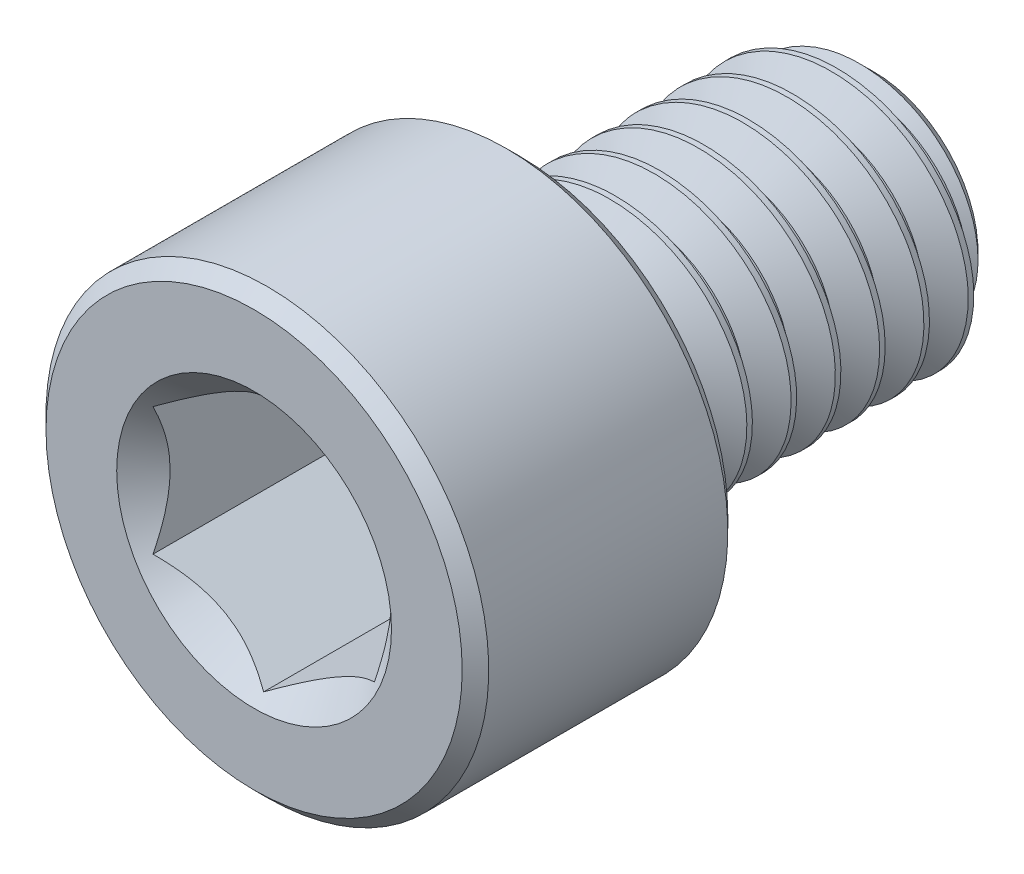
SolidWorks part; units mm, degrees
ref_plane "Front Plane" through (0, 0, 0) normal (0, 0, 1) x (1, 0, 0)
ref_plane "Top Plane" through (0, 0, 0) normal (0, 1, 0) x (1, 0, 0)
ref_plane "Right Plane" through (0, 0, 0) normal (1, 0, 0) x (0, 0, -1)
sketch "Sketch1" plane through (0, 0, 0) normal (1, 0, 0) x (0, 0, -1)
  line L0 (-7, 0) -> (7, 0) construction
  line L1 (7, 0) -> (7, 2.3505) construction
  line L2 (7, 2.3505) -> (6.3505, 3) construction
  line L3 (6.3505, 3) -> (6.25, 3) construction
  line L4 (6.25, 3) -> (-1, 3) construction
  line L5 (-1, 3) -> (-1, 5) construction
  line L6 (-1, 5) -> (-7, 5) construction
  line L7 (-7, 5) -> (-7, 0) construction
  line L8 (7, 2.3505) -> (7, 3) construction
  line L9 (6.9375, 3.1083) -> (7.4375, 2.2422) construction
  line L10 (7.4375, 2.2422) -> (7.9375, 3.1083) construction
  line L11 (7.9375, 3.1083) -> (6.9375, 3.1083) construction
  line L12 (7.4375, 3.1083) -> (7.4375, 3) construction
  line L13 (7.4375, 2.2422) -> (7.4375, 2.3505) construction
  line L14 (7.375, 2.3505) -> (7.5, 2.3505) construction
  line L15 (7, 3) -> (7.875, 3) construction
  line L16 (6.9687, 3.0541) -> (7.9063, 3.0541) construction
  line L17 (7, 0) -> (7, -3) construction
  line L18 (-1.3, 5) -> (-1, 4.7) construction
  line L19 (-6.7, 5) -> (-7, 4.7) construction
  line L20 (-1, 3) -> (-1, 0) construction
  line L21 (-1, 1.5) -> (1.6667, 1.5) construction
  line L22 (1.6667, 1.5) -> (4.3333, 1.5) construction
  line L23 (4.3333, 1.5) -> (7, 1.5) construction
  line L24 (1.6667, 1.5) -> (1.6667, 3) construction
  line L25 (1.6667, 3) -> (1.6667, 5) construction
  line L26 (4.3333, 1.5) -> (4.3333, 5) construction
  point P0 (-7, 2.5)
  point P3 (4.5, 3)
  point P4 (0, 0)
  point P18 (4.3333, 3)
  point P22 (7.4375, 2.3505)
  point P24 (6.25, 3)
  point P25 (7.4375, 3)
  point P28 (7.4375, 3.0541)
  point P29 (4.5, -3)
  point P30 (1.6667, 3)
  point P31 (-4, 5)
  point P37 (-2.05, 5)
  point P38 (-6.55, 5)
  point P45 (1.6667, 1.5)
  point P46 (4.3333, 1.5)
  dimension "D2" = 0.125
  dimension "D7" = 0.3
  dimension "D8" = 0.3
  dimension "D9" = 0.3
  dimension "D10" = 0.15
  dimension "D11" = 0.75
  dimension "Drive Size" = 5
  dimension "Head Diameter" = 10
  dimension "Head Height" = 6
  dimension "Thread Pitch" = 1
  dimension "Thread Dia" = 6
  dimension "Length" = 8
  dimension "D12" = 0.75
  dimension "D4" = 2.5
  dimension "D3" = 45
sketch "Sketch2" plane through (0, 0, 0) normal (1, 0, 0) x (0, 0, -1)
  line L0 (-7, 0) -> (-7, 4.7)
  line L1 (-6.7, 5) -> (-1.3, 5)
  line L2 (-1, 4.7) -> (-1, 3.3)
  line L4 (6.3505, 3) -> (7, 2.3505)
  line L5 (7, 2.3505) -> (7, 0)
  line L6 (-1, 5) -> (-7, 5) construction
  line L7 (7, 0) -> (-7, 0)
  line L8 (-6.7, 5) -> (-7, 4.7) construction
  line L10 (-6.7, 5) -> (-7, 4.7)
  line L14 (-1.3, 5) -> (-1, 4.7) construction
  line L16 (-1.3, 5) -> (-1, 4.7)
  line L17 (-1, 3) -> (-1, 5) construction
  line L19 (-0.7, 3) -> (6.3505, 3)
  line L20 (6.25, 3) -> (-1, 3) construction
  arc A1 (-1, 3.3) -> (-0.7, 3) centre (-0.7, 3.3) ccw
  dimension "D3" = 0.3
revolve "Revolve1" add sketch "Sketch2" angle 360 about L7
sketch "Sketch3" plane through (0, 0, 7) normal (0, 0, 1) x (1, 0, 0)
  line L1 (2.5, -1.4434) -> (2.5, 1.4434)
  line L2 (2.5, 1.4434) -> (0, 2.8868)
  line L3 (0, 2.8868) -> (-2.5, 1.4434)
  line L4 (-2.5, 1.4434) -> (-2.5, -1.4434)
  line L5 (-2.5, -1.4434) -> (0, -2.8868)
  line L6 (0, -2.8868) -> (2.5, -1.4434)
  circle A0 centre (0, 0) radius 2.5 construction
  circle A1 centre (0, 0) radius 5 construction
  circle A2 centre (0, 0) radius 5 construction
  circle A3 centre (0, 0) radius 2.8868 construction
  point P13 (0, 0)
  dimension "D1" = 5.7735
extrude "Cut-Extrude1" cut sketch "Sketch3" against normal offset from surface (5 mm away) 1 up to face at (0, 4.7, 1)
sketch "Sketch4" plane through (0, 0, 7) normal (0, 0, 1) x (1, 0, 0)
  circle A0 centre (0, 0) radius 3.1033
  dimension "D1" = 6.2065
extrude "Cut-Extrude2" cut sketch "Sketch4" against normal up to vertex (3 mm away) draft 45 up to point (0, 5, 4)
sketch "Sketch11" plane through (0, 0, 0) normal (1, 0, 0) x (0, 0, -1)
  line L0 (-7, 0) -> (7, 0) construction
  line L1 (-7, 0) -> (7, 0) construction
  line L2 (0.5, 0) -> (0.5, 3) construction
  line L3 (6.25, 3) -> (-1, 3) construction
  line L4 (5.5, 0) -> (5.5, 3) construction
  line L6 (7, 2.3505) -> (7, 3) construction
  point P2 (0.5, 0)
  point P3 (5.5, 0)
  dimension "D1" = 1.5
  dimension "D2" = 1.5
sketch "Sketch6" plane through (0, 0, -7) normal (0, 0, -1) x (-1, 0, 0)
  circle A0 centre (0, 0) radius 3
curve "Helix/Spiral1" pitch 1 height 9 radius 3 centre (0, 0, -7) axis (0, 0, 1) start towards (0, 1, 0)
sketch "Sketch10" plane through (0, 0, 0) normal (1, 0, 0) x (0, 0, -1)
  line L0 (-0.7, -5) -> (-0.7, 5)
  line L5 (-7, 0) -> (7, 0) construction
  line L6 (-0.7, 3) -> (-0.7, -3) construction
  point P3 (-0.7, 0)
split "Split1" trim tools "Sketch10" bodies to split 106 resulting bodies 114 115
sketch "Sketch7" plane through (0, 0, 0) normal (1, 0, 0) x (0, 0, -1)
  line L0 (6.9687, 3.0541) -> (7.9063, 3.0541)
  line L1 (7.9063, 3.0541) -> (7.5, 2.3505)
  line L2 (7.5, 2.3505) -> (7.375, 2.3505)
  line L3 (7.375, 2.3505) -> (6.9687, 3.0541)
sweep "Cut-Sweep1" cut profiles "Sketch7" path "Helix/Spiral1" align with end faces yes
sketch "Sketch8" plane through (0, 0, 0) normal (1, 0, 0) x (0, 0, -1)
  line L0 (-1, 0) -> (-1, 3)
  line L1 (-0.7, -3) -> (-0.7, 3) construction
  line L2 (-1, 3) -> (-0.7, 3)
  line L4 (-0.7, 3) -> (1.0321, 0)
  line L5 (1.0321, 0) -> (-1, 0)
  line L6 (6.25, 3) -> (-1, 3) construction
  line L7 (-7, 0) -> (7, 0) construction
  dimension "D1" = 60
revolve "Revolve2" add sketch "Sketch8" angle 360 about L5
equation "\"D2@Sketch1\" = \"Thread Pitch@Sketch1\" / 8"
equation "\"D4@Helix/Spiral1\" = \"Thread Pitch@Sketch1\""
equation "\"D7@Sketch1\" = \"Head Height@Sketch1\" * .05"
equation "\"D8@Sketch1\"=\"D7@Sketch1\""
equation "\"D9@Sketch1\"=\"D7@Sketch1\""
equation "\"D10@Sketch1\"=\"D7@Sketch1\"/2"
equation "\"D11@Sketch1\"=\"D10@Sketch1\"*5"
equation "\"D4@Sketch1\"=\"Thread Pitch@Sketch1\"*2.5"
equation "\"D12@Sketch1\"=\"Thread Pitch@Sketch1\"*.75"
equation "\"D3@Helix/Spiral1\"=\"Length@Sketch1\"+\"Thread Pitch@Sketch1\""
equation "\"D3@Sketch2\"=\"Thread Dia@Sketch1\"*0.05"
equation "\"D1@Sketch11\"=\"Length@Sketch1\"*0.1875"
equation "\"D2@Sketch11\"=\"D1@Sketch11\""
equation "\"D1@Sketch4\"=\"D1@Sketch3\"*1.075"
